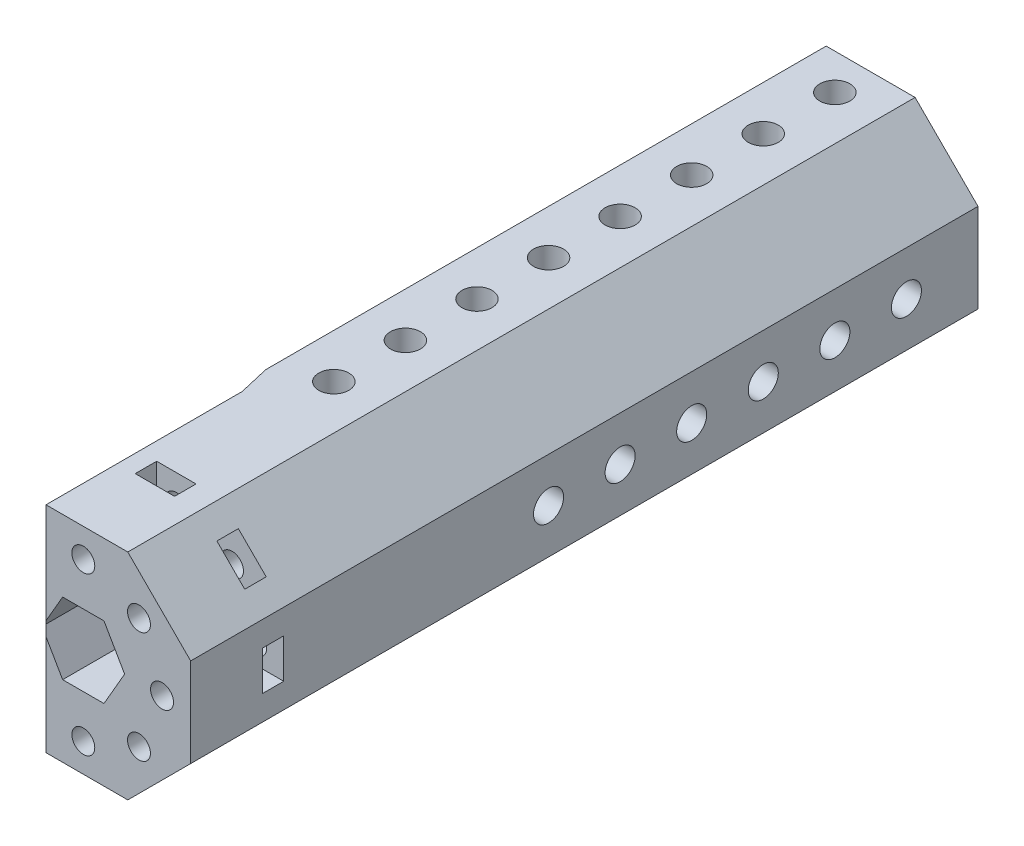
SolidWorks part; units mm, degrees
ref_plane "Alzado" through (0, 0, 0) normal (0, 0, 1) x (1, 0, 0)
ref_plane "Planta" through (0, 0, 0) normal (0, 1, 0) x (1, 0, 0)
ref_plane "Vista lateral" through (0, 0, 0) normal (1, 0, 0) x (0, 0, -1)
sketch "Croquis1" plane through (0, 0, 0) normal (0, 0, 1) x (1, 0, 0)
  line L1 (15, -6.2132) -> (15, 6.2132)
  line L2 (15, 6.2132) -> (6.2132, 15)
  line L3 (6.2132, 15) -> (-6.2132, 15)
  line L4 (-6.2132, 15) -> (-15, 6.2132)
  line L5 (-15, 6.2132) -> (-15, -6.2132)
  line L6 (-15, -6.2132) -> (-6.2132, -15)
  line L7 (-6.2132, -15) -> (6.2132, -15)
  line L8 (6.2132, -15) -> (15, -6.2132)
  circle A0 centre (0, 0) radius 15 construction
  dimension "D1" = 30
extrude "Saliente-Extruir1" add sketch "Croquis1" along normal blind 55
sketch "Croquis8" plane through (0, -15, 0) normal (0, -1, 0) x (1, 0, 0)
  line L0 (-6.2132, 0) -> (6.2132, 0) construction
  circle A0 centre (0, 5) radius 2.1
  point P5 (0, 0)
  dimension "D1" = 4.2
  dimension "D2" = 5
mirror "Simetría1" about plane through (0, 0, 55) normal (0, 0, 1) of "Saliente-Extruir1"
sketch "Croquis4" plane through (0, 0, 0) normal (0, 0, -1) x (-1, 0, 0)
  line L1 (-5.7735, 0) -> (-2.8868, -5)
  line L2 (-2.8868, -5) -> (2.8868, -5)
  line L3 (2.8868, -5) -> (5.7735, 0)
  line L4 (5.7735, 0) -> (2.8868, 5)
  line L5 (2.8868, 5) -> (-2.8868, 5)
  line L6 (-2.8868, 5) -> (-5.7735, 0)
  circle A1 centre (0, 0) radius 5 construction
  point P3 (-6.9664, 0.4944)
  point P11 (4.6263, -8.0129)
  dimension "D2" = 10
extrude "Cortar-Extruir3" cut sketch "Croquis4" against normal through all
sketch "Croquis5" plane through (0, -15, 0) normal (0, -1, 0) x (1, 0, 0)
  line L0 (-6.2132, 110) -> (-6.2132, 78.2987)
  line L1 (-6.2132, 110) -> (-6.2132, 0) construction
  line L2 (-6.2132, 78.2987) -> (-15, 40.5695)
  line L3 (-15, 110) -> (-15, 0) construction
  line L4 (-15, 40.5695) -> (-15, 110)
  line L5 (-15, 110) -> (-6.2132, 110)
extrude "Cortar-Extruir4" cut sketch "Croquis5" against normal through all
sketch "Croquis6" plane through (0, 0, 110) normal (0, 0, 1) x (1, 0, 0)
  circle A0 centre (0, 11) radius 1.6
  circle A2 centre (7.7782, 7.7782) radius 1.6
  circle A3 centre (11, 0) radius 1.6
  circle A4 centre (7.7782, -7.7782) radius 1.6
  circle A5 centre (0, -11) radius 1.6
  circle A9 centre (-7.7782, 7.7782) radius 1.6 [skipped]
  circle A10 centre (-11, 0) radius 1.6 [skipped]
  circle A11 centre (-7.7782, -7.7782) radius 1.6 [skipped]
  point P22 (0, 0)
  dimension "D1" = 3.2
  dimension "D2" = 11
  dimension "D4" = 8
sketch "Croquis7" plane through (0, 0, 110) normal (0, 0, 1) x (1, 0, 0)
  line L0 (-2.75, 12.5877) -> (-2.75, 18.4632)
  line L1 (2.75, 12.5877) -> (0, 14.1754) construction
  line L2 (0, 14.1754) -> (-2.75, 12.5877) construction
  line L3 (-2.75, 12.5877) -> (-2.75, 9.4123)
  line L4 (-2.75, 9.4123) -> (0, 7.8246)
  line L5 (0, 7.8246) -> (2.75, 9.4123)
  line L6 (2.75, 9.4123) -> (2.75, 12.5877)
  line L8 (-2.75, 18.4632) -> (2.75, 23.9632)
  line L9 (2.75, 23.9632) -> (2.75, 12.5877)
  line L10 (6.9563, 10.8454) -> (11.1109, 15)
  line L11 (6.9563, 10.8454) -> (4.7109, 8.6)
  line L12 (4.7109, 8.6) -> (5.5328, 5.5328)
  line L13 (5.5328, 5.5328) -> (8.6, 4.7109)
  line L14 (8.6, 4.7109) -> (10.8454, 6.9563)
  line L15 (11.1109, 15) -> (18.8891, 15)
  line L16 (18.8891, 15) -> (10.8454, 6.9563)
  line L17 (10.8454, 6.9563) -> (10.0235, 10.0235) construction
  line L18 (10.0235, 10.0235) -> (6.9563, 10.8454) construction
  line L19 (12.5877, 2.75) -> (18.4632, 2.75)
  line L20 (12.5877, 2.75) -> (9.4123, 2.75)
  line L21 (9.4123, 2.75) -> (7.8246, 0)
  line L22 (7.8246, 0) -> (9.4123, -2.75)
  line L23 (9.4123, -2.75) -> (12.5877, -2.75)
  line L24 (18.4632, 2.75) -> (23.9632, -2.75)
  line L25 (23.9632, -2.75) -> (12.5877, -2.75)
  line L26 (12.5877, -2.75) -> (14.1754, 0) construction
  line L27 (14.1754, 0) -> (12.5877, 2.75) construction
  line L28 (10.8454, -6.9563) -> (15, -11.1109)
  line L29 (10.8454, -6.9563) -> (8.6, -4.7109)
  line L30 (8.6, -4.7109) -> (5.5328, -5.5328)
  line L31 (5.5328, -5.5328) -> (4.7109, -8.6)
  line L32 (4.7109, -8.6) -> (6.9563, -10.8454)
  line L33 (15, -11.1109) -> (15, -18.8891)
  line L34 (15, -18.8891) -> (6.9563, -10.8454)
  line L35 (6.9563, -10.8454) -> (10.0235, -10.0235) construction
  line L36 (10.0235, -10.0235) -> (10.8454, -6.9563) construction
  line L37 (2.75, -12.5877) -> (2.75, -18.4632)
  line L38 (2.75, -12.5877) -> (2.75, -9.4123)
  line L39 (2.75, -9.4123) -> (0, -7.8246)
  line L40 (0, -7.8246) -> (-2.75, -9.4123)
  line L41 (-2.75, -9.4123) -> (-2.75, -12.5877)
  line L42 (2.75, -18.4632) -> (-2.75, -23.9632)
  line L43 (-2.75, -23.9632) -> (-2.75, -12.5877)
  line L44 (-2.75, -12.5877) -> (0, -14.1754) construction
  line L45 (0, -14.1754) -> (2.75, -12.5877) construction
  line L46 (-6.9563, -10.8454) -> (-11.1109, -15) construction
  line L47 (-6.9563, -10.8454) -> (-4.7109, -8.6) construction
  line L48 (-4.7109, -8.6) -> (-5.5328, -5.5328) construction
  line L49 (-5.5328, -5.5328) -> (-8.6, -4.7109) construction
  line L50 (-8.6, -4.7109) -> (-10.8454, -6.9563) construction
  line L51 (-11.1109, -15) -> (-18.8891, -15) construction
  line L52 (-18.8891, -15) -> (-10.8454, -6.9563) construction
  line L53 (-10.8454, -6.9563) -> (-10.0235, -10.0235) construction
  line L54 (-10.0235, -10.0235) -> (-6.9563, -10.8454) construction
  line L55 (-12.5877, -2.75) -> (-18.4632, -2.75) construction
  line L56 (-12.5877, -2.75) -> (-9.4123, -2.75) construction
  line L57 (-9.4123, -2.75) -> (-7.8246, 0) construction
  line L58 (-7.8246, 0) -> (-9.4123, 2.75) construction
  line L59 (-9.4123, 2.75) -> (-12.5877, 2.75) construction
  line L60 (-18.4632, -2.75) -> (-23.9632, 2.75) construction
  line L61 (-23.9632, 2.75) -> (-12.5877, 2.75) construction
  line L62 (-12.5877, 2.75) -> (-14.1754, 0) construction
  line L63 (-14.1754, 0) -> (-12.5877, -2.75) construction
  line L64 (-10.8454, 6.9563) -> (-15, 11.1109) construction
  line L65 (-10.8454, 6.9563) -> (-8.6, 4.7109) construction
  line L66 (-8.6, 4.7109) -> (-5.5328, 5.5328) construction
  line L67 (-5.5328, 5.5328) -> (-4.7109, 8.6) construction
  line L68 (-4.7109, 8.6) -> (-6.9563, 10.8454) construction
  line L69 (-15, 11.1109) -> (-15, 18.8891) construction
  line L70 (-15, 18.8891) -> (-6.9563, 10.8454) construction
  line L71 (-6.9563, 10.8454) -> (-10.0235, 10.0235) construction
  line L72 (-10.0235, 10.0235) -> (-10.8454, 6.9563) construction
  circle A0 centre (0, 11) radius 2.75 construction
  circle A1 centre (7.7782, 7.7782) radius 2.75 construction
  circle A2 centre (11, 0) radius 2.75 construction
  circle A3 centre (7.7782, -7.7782) radius 2.75 construction
  circle A4 centre (0, -11) radius 2.75 construction
  circle A5 centre (-7.7782, -7.7782) radius 2.75 construction
  circle A6 centre (-11, 0) radius 2.75 construction
  circle A7 centre (-7.7782, 7.7782) radius 2.75 construction
  point P86 (0, 0)
  dimension "D1" = 5.5
  dimension "D2" = 8
extrude "Cortar-Extruir5" cut sketch "Croquis6" against normal blind 20
extrude "Cortar-Extruir6" cut sketch "Croquis7" against normal blind 3 from offset 10 offset against normal yes
extrude "Cortar-Extruir8" cut sketch "Croquis8" against normal through all
pattern_linear "MatrizL1" count 8 spacing 10 along (0, 0, 1) of "Cortar-Extruir8"
chamfer "Chaflán1" distance 1 angle 45 3 edges at (-6.2132, 15, 94.1494) (-6.2132, -15, 94.1494) (-6.2132, 0, 110)
sketch "Croquis9" plane through (15, 0, -15) normal (-1, 0, 0) x (0, 0, -1)
  line L1 (-15, 6.2132) -> (-15, -6.2132) construction
  circle A0 centre (-25, 0) radius 2.1
  point P2 (-48.6813, 0)
  point P3 (0, 0)
  dimension "D1" = 4.2
  dimension "D2" = 10
extrude "Cortar-Extruir11" cut sketch "Croquis9" along normal through all
pattern_linear "MatrizL2" count 6 spacing 10 along (0, 0, 1) of "Cortar-Extruir11"
